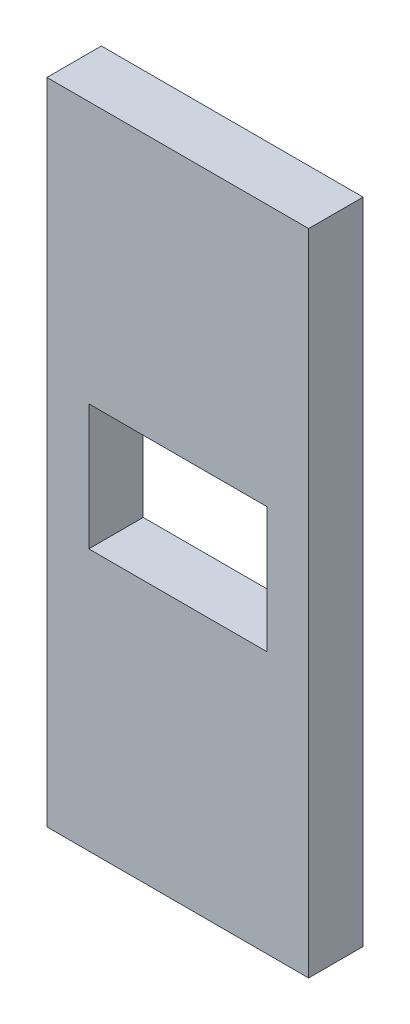
SolidWorks part; units mm, degrees
ref_plane "Front Plane" through (0, 0, 0) normal (0, 0, 1) x (1, 0, 0)
ref_plane "Top Plane" through (0, 0, 0) normal (0, 1, 0) x (1, 0, 0)
ref_plane "Right Plane" through (0, 0, 0) normal (1, 0, 0) x (0, 0, -1)
sketch "Sketch1" plane through (0, 0, 0) normal (0, 0, 1) x (1, 0, 0)
  line L0 (0, 62) -> (0, 42)
  line L1 (0, 62) -> (25, 62)
  line L2 (0, 42) -> (0, 37)
  line L3 (25, 0) -> (0, 0)
  line L4 (4, 37) -> (21, 37)
  line L5 (4, 25) -> (21, 25)
  line L6 (4, 37) -> (4, 25)
  line L7 (21, 37) -> (21, 25)
  line L8 (0, 42) -> (25, 42) construction
  line L9 (0, 37) -> (25, 37) construction
  line L10 (0, 37) -> (0, 25)
  line L11 (0, 25) -> (0, 20)
  line L12 (25, 42) -> (25, 37)
  line L13 (25, 62) -> (25, 42)
  line L14 (0, 20) -> (0, 0)
  line L15 (25, 37) -> (25, 25)
  line L16 (25, 25) -> (25, 20)
  line L17 (25, 20) -> (25, 0)
  line L18 (0, 25) -> (25, 25) construction
  line L19 (25, 20) -> (0, 20) construction
  line L20 (12.5, -0.0005) -> (12.5, 4.0956) construction
  point P18 (12.5, 25)
  point P20 (12.5, 37)
  point P21 (12.5, 62)
  dimension "D1" = 20
  dimension "D2" = 12
  dimension "D3" = 5
  dimension "D4" = 25
  dimension "D5" = 12
  dimension "D6" = 17
extrude "Boss-Extrude1" add sketch "Sketch1" along normal blind 5.2
